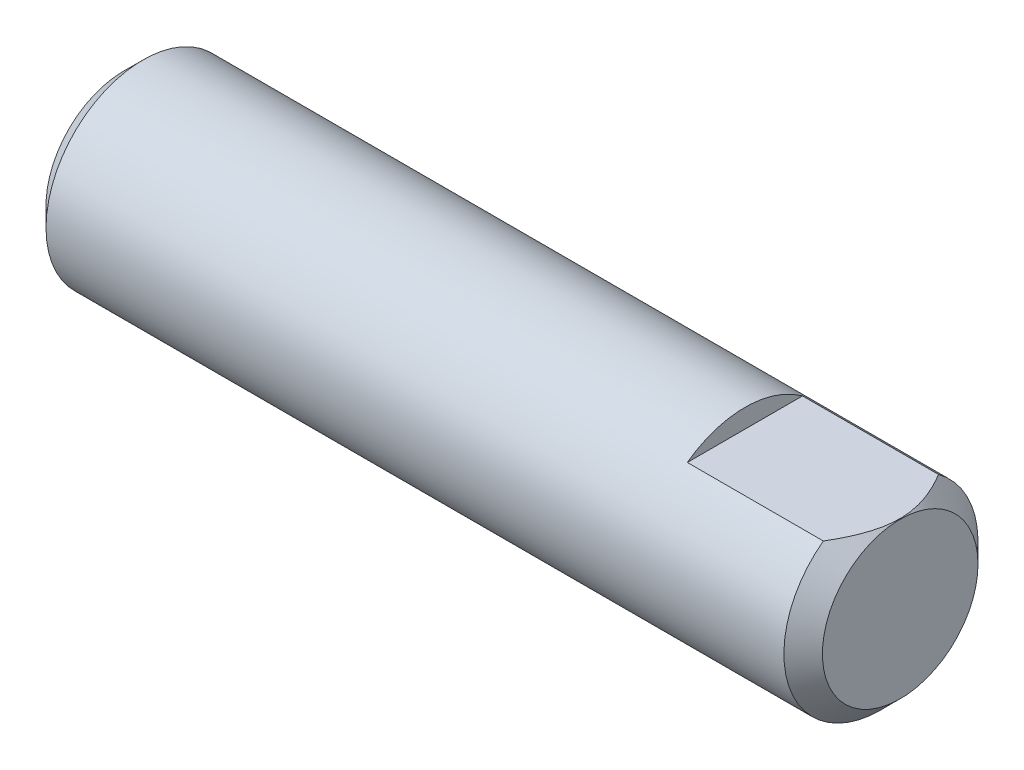
SolidWorks part; units mm, degrees
material "316L ST. STL."
ref_plane "Front" through (0, 0, 0) normal (0, 0, 1) x (1, 0, 0)
ref_plane "Top" through (0, 0, 0) normal (0, 1, 0) x (1, 0, 0)
ref_plane "Right" through (0, 0, 0) normal (1, 0, 0) x (0, 0, -1)
ref_axis "Axis1" through (0, 50, 0) along (0, -1, 0)
sketch "Sketch1" plane through (0, 0, 0) normal (1, 0, 0) x (0, 0, -1)
  circle A0 centre (0, 0) radius 3.9688
  dimension "D1" = 7.9375
extrude "Extrude1" add sketch "Sketch1" along normal blind 31.75
chamfer "Chamfer1" distance 0.7874 angle 45 2 edges at (0, 0, -3.9688) (31.75, 0, -3.9688)
sketch "Sketch2" plane through (31.75, 0, 0) normal (1, 0, 0) x (0, 0, -1)
  line L1 (-3.81, 4.464) -> (3.81, 4.464)
  line L2 (-3.81, 4.464) -> (-3.81, 3.194)
  line L3 (-3.81, 3.194) -> (3.81, 3.194)
  line L4 (3.81, 4.464) -> (3.81, 3.194)
  circle A1 centre (0, 0) radius 3.9688 construction
  point P6 (0, 3.194)
  dimension "D1" = 7.1628
  dimension "D2" = 7.62
  dimension "D3" = 1.27
extrude "Extrude2" cut sketch "Sketch2" against normal blind 6.35
